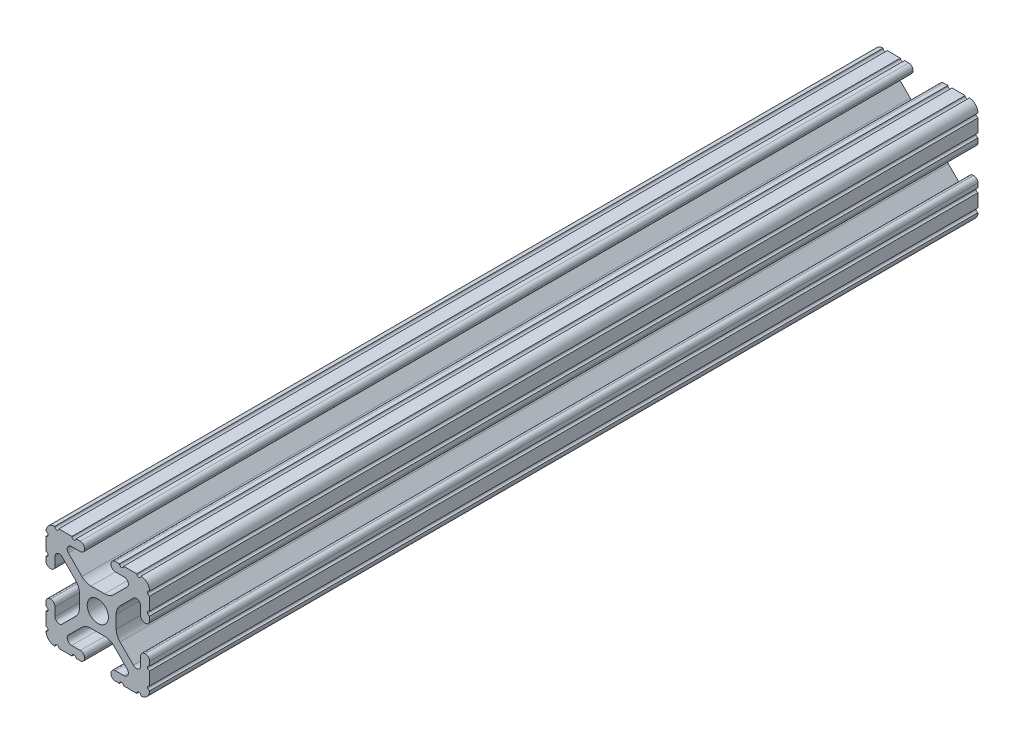
SolidWorks part; units mm, degrees
ref_plane "Front Plane" through (0, 0, 0) normal (0, 0, 1) x (1, 0, 0)
ref_plane "Top Plane" through (0, 0, 0) normal (0, 1, 0) x (1, 0, 0)
ref_plane "Right Plane" through (0, 0, 0) normal (1, 0, 0) x (0, 0, -1)
sketch "Sketch1" plane through (0, 0, 0) normal (0, 0, 1) x (1, 0, 0)
  line L88 (-7.1797, -8.6452) -> (-3.9523, -5.4237)
  line L89 (-1.7093, -4.4958) -> (1.7093, -4.4958)
  line L90 (3.9523, -5.4237) -> (7.1797, -8.6452)
  line L91 (6.4164, -10.4902) -> (4.2875, -10.4902)
  line L92 (3.2385, -11.5392) -> (3.2385, -11.651)
  line L93 (4.2875, -12.7) -> (5.3171, -12.7)
  line L94 (6.3331, -12.7) -> (9.5504, -12.7)
  line L95 (12.7, -9.5504) -> (12.7, -6.3331)
  line L96 (12.7, -5.3171) -> (12.7, -4.2875)
  line L97 (11.651, -3.2385) -> (11.5392, -3.2385)
  line L98 (10.4902, -4.2875) -> (10.4902, -6.4021)
  line L99 (8.7371, -7.1294) -> (5.441, -3.8408)
  line L100 (4.5085, -1.5932) -> (4.5085, 1.5932)
  line L101 (5.441, 3.8408) -> (8.7371, 7.1294)
  line L102 (10.4902, 6.4021) -> (10.4902, 4.2875)
  line L103 (11.5392, 3.2385) -> (11.651, 3.2385)
  line L104 (12.7, 4.2875) -> (12.7, 5.3171)
  line L105 (12.7, 6.3331) -> (12.7, 9.5504)
  line L106 (9.5504, 12.7) -> (6.3331, 12.7)
  line L107 (5.3171, 12.7) -> (4.2875, 12.7)
  line L108 (3.2385, 11.651) -> (3.2385, 11.5392)
  line L109 (4.2875, 10.4902) -> (6.4768, 10.4902)
  line L110 (7.207, 8.7244) -> (3.8983, 5.4232)
  line L111 (1.6558, 4.4958) -> (-1.6558, 4.4958)
  line L112 (-3.8983, 5.4232) -> (-7.207, 8.7244)
  line L113 (-6.4768, 10.4902) -> (-4.2875, 10.4902)
  line L114 (-3.2385, 11.5392) -> (-3.2385, 11.651)
  line L115 (-4.2875, 12.7) -> (-5.3171, 12.7)
  line L116 (-6.3331, 12.7) -> (-9.5504, 12.7)
  line L117 (-12.7, 9.5504) -> (-12.7, 6.3331)
  line L118 (-12.7, 5.3171) -> (-12.7, 4.2875)
  line L119 (-11.651, 3.2385) -> (-11.5392, 3.2385)
  line L120 (-10.4902, 4.2875) -> (-10.4902, 6.4021)
  line L121 (-8.7371, 7.1294) -> (-5.441, 3.8408)
  line L122 (-4.5085, 1.5932) -> (-4.5085, -1.5932)
  line L123 (-5.441, -3.8408) -> (-8.7371, -7.1294)
  line L124 (-10.4902, -6.4021) -> (-10.4902, -4.2875)
  line L125 (-11.5392, -3.2385) -> (-11.651, -3.2385)
  line L126 (-12.7, -4.2875) -> (-12.7, -5.3171)
  line L127 (-12.7, -6.3331) -> (-12.7, -9.5504)
  line L128 (-9.5504, -12.7) -> (-6.3331, -12.7)
  line L129 (-5.3171, -12.7) -> (-4.2875, -12.7)
  line L130 (-3.2385, -11.651) -> (-3.2385, -11.5392)
  line L131 (-4.2875, -10.4902) -> (-6.4164, -10.4902)
  circle A1 centre (0, 0) radius 2.6035
  arc A104 (-7.1797, -8.6452) -> (-6.4164, -10.4902) centre (-6.4164, -9.4098) ccw
  arc A105 (-1.7093, -4.4958) -> (-3.9523, -5.4237) centre (-1.7093, -7.6708) ccw
  arc A106 (3.9523, -5.4237) -> (1.7093, -4.4958) centre (1.7093, -7.6708) ccw
  arc A107 (6.4164, -10.4902) -> (7.1797, -8.6452) centre (6.4164, -9.4098) ccw
  arc A108 (4.2875, -10.4902) -> (3.2385, -11.5392) centre (4.2875, -11.5392) ccw
  arc A109 (3.2385, -11.651) -> (4.2875, -12.7) centre (4.2875, -11.651) ccw
  arc A110 (6.3331, -12.7) -> (5.3171, -12.7) centre (5.8251, -12.7) ccw
  arc A111 (10.5664, -12.6998) -> (9.5504, -12.7) centre (10.0584, -12.7) ccw
  arc A112 (10.5664, -12.6998) -> (12.6998, -10.5664) centre (10.5918, -10.5918) ccw
  arc A113 (12.7, -9.5504) -> (12.6998, -10.5664) centre (12.7, -10.0584) ccw
  arc A114 (12.7, -5.3171) -> (12.7, -6.3331) centre (12.7, -5.8251) ccw
  arc A115 (12.7, -4.2875) -> (11.651, -3.2385) centre (11.651, -4.2875) ccw
  arc A116 (11.5392, -3.2385) -> (10.4902, -4.2875) centre (11.5392, -4.2875) ccw
  arc A117 (8.7371, -7.1294) -> (10.4902, -6.4021) centre (9.4628, -6.4021) ccw
  arc A118 (4.5085, -1.5932) -> (5.441, -3.8408) centre (7.6835, -1.5932) ccw
  arc A119 (5.441, 3.8408) -> (4.5085, 1.5932) centre (7.6835, 1.5932) ccw
  arc A120 (10.4902, 6.4021) -> (8.7371, 7.1294) centre (9.4628, 6.4021) ccw
  arc A121 (10.4902, 4.2875) -> (11.5392, 3.2385) centre (11.5392, 4.2875) ccw
  arc A122 (11.651, 3.2385) -> (12.7, 4.2875) centre (11.651, 4.2875) ccw
  arc A123 (12.7, 6.3331) -> (12.7, 5.3171) centre (12.7, 5.8251) ccw
  arc A124 (12.6998, 10.5664) -> (12.7, 9.5504) centre (12.7, 10.0584) ccw
  arc A125 (12.6998, 10.5664) -> (10.5664, 12.6998) centre (10.5918, 10.5918) ccw
  arc A126 (9.5504, 12.7) -> (10.5664, 12.6998) centre (10.0584, 12.7) ccw
  arc A127 (5.3171, 12.7) -> (6.3331, 12.7) centre (5.8251, 12.7) ccw
  arc A128 (4.2875, 12.7) -> (3.2385, 11.651) centre (4.2875, 11.651) ccw
  arc A129 (3.2385, 11.5392) -> (4.2875, 10.4902) centre (4.2875, 11.5392) ccw
  arc A130 (7.207, 8.7244) -> (6.4768, 10.4902) centre (6.4768, 9.4563) ccw
  arc A131 (1.6558, 4.4958) -> (3.8983, 5.4232) centre (1.6558, 7.6708) ccw
  arc A132 (-3.8983, 5.4232) -> (-1.6558, 4.4958) centre (-1.6558, 7.6708) ccw
  arc A133 (-6.4768, 10.4902) -> (-7.207, 8.7244) centre (-6.4768, 9.4563) ccw
  arc A134 (-4.2875, 10.4902) -> (-3.2385, 11.5392) centre (-4.2875, 11.5392) ccw
  arc A135 (-3.2385, 11.651) -> (-4.2875, 12.7) centre (-4.2875, 11.651) ccw
  arc A136 (-6.3331, 12.7) -> (-5.3171, 12.7) centre (-5.8251, 12.7) ccw
  arc A137 (-10.5664, 12.6998) -> (-9.5504, 12.7) centre (-10.0584, 12.7) ccw
  arc A138 (-10.5664, 12.6998) -> (-12.6998, 10.5664) centre (-10.5918, 10.5918) ccw
  arc A139 (-12.7, 9.5504) -> (-12.6998, 10.5664) centre (-12.7, 10.0584) ccw
  arc A140 (-12.7, 5.3171) -> (-12.7, 6.3331) centre (-12.7, 5.8251) ccw
  arc A141 (-12.7, 4.2875) -> (-11.651, 3.2385) centre (-11.651, 4.2875) ccw
  arc A142 (-11.5392, 3.2385) -> (-10.4902, 4.2875) centre (-11.5392, 4.2875) ccw
  arc A143 (-8.7371, 7.1294) -> (-10.4902, 6.4021) centre (-9.4628, 6.4021) ccw
  arc A144 (-4.5085, 1.5932) -> (-5.441, 3.8408) centre (-7.6835, 1.5932) ccw
  arc A145 (-5.441, -3.8408) -> (-4.5085, -1.5932) centre (-7.6835, -1.5932) ccw
  arc A146 (-10.4902, -6.4021) -> (-8.7371, -7.1294) centre (-9.4628, -6.4021) ccw
  arc A147 (-10.4902, -4.2875) -> (-11.5392, -3.2385) centre (-11.5392, -4.2875) ccw
  arc A148 (-11.651, -3.2385) -> (-12.7, -4.2875) centre (-11.651, -4.2875) ccw
  arc A149 (-12.7, -6.3331) -> (-12.7, -5.3171) centre (-12.7, -5.8251) ccw
  arc A150 (-12.6998, -10.5664) -> (-12.7, -9.5504) centre (-12.7, -10.0584) ccw
  arc A151 (-12.6998, -10.5664) -> (-10.5664, -12.6998) centre (-10.5918, -10.5918) ccw
  arc A152 (-9.5504, -12.7) -> (-10.5664, -12.6998) centre (-10.0584, -12.7) ccw
  arc A153 (-5.3171, -12.7) -> (-6.3331, -12.7) centre (-5.8251, -12.7) ccw
  arc A154 (-4.2875, -12.7) -> (-3.2385, -11.651) centre (-4.2875, -11.651) ccw
  arc A155 (-3.2385, -11.5392) -> (-4.2875, -10.4902) centre (-4.2875, -11.5392) ccw
extrude "Boss-Extrude1" add sketch "Sketch1" along normal mid plane 609.6
sketch "Sketch2" plane through (12.7, 0, 0) normal (1, 0, 0) x (0, 0, -1)
  line L0 (-56.5865, 13.6438) -> (-56.5865, -14.2345) construction
  line L1 (-56.5865, -14.2345) -> (310.7431, -14.2345)
  line L2 (310.7431, -14.2345) -> (310.7431, 13.6438)
  line L3 (310.7431, 13.6438) -> (-56.5865, 13.6438)
  line L4 (-56.5865, 13.6438) -> (-86.1277, 13.6438)
  line L6 (-56.5865, -14.2345) -> (-86.1277, -14.2345)
  line L8 (-86.1277, -14.2345) -> (-86.1277, 13.6438)
  line L9 (-305.4758, 13.3523) -> (-289.2182, 13.3523)
  line L10 (-305.4758, 13.3523) -> (-305.4758, -14.2345)
  line L11 (-305.4758, -14.2345) -> (-289.2182, -14.2345)
  line L12 (-289.2182, 13.3523) -> (-289.2182, -14.2345)
extrude "Cut-Extrude1" cut sketch "Sketch2" against normal blind 26.162 and the other way blind 1.778
